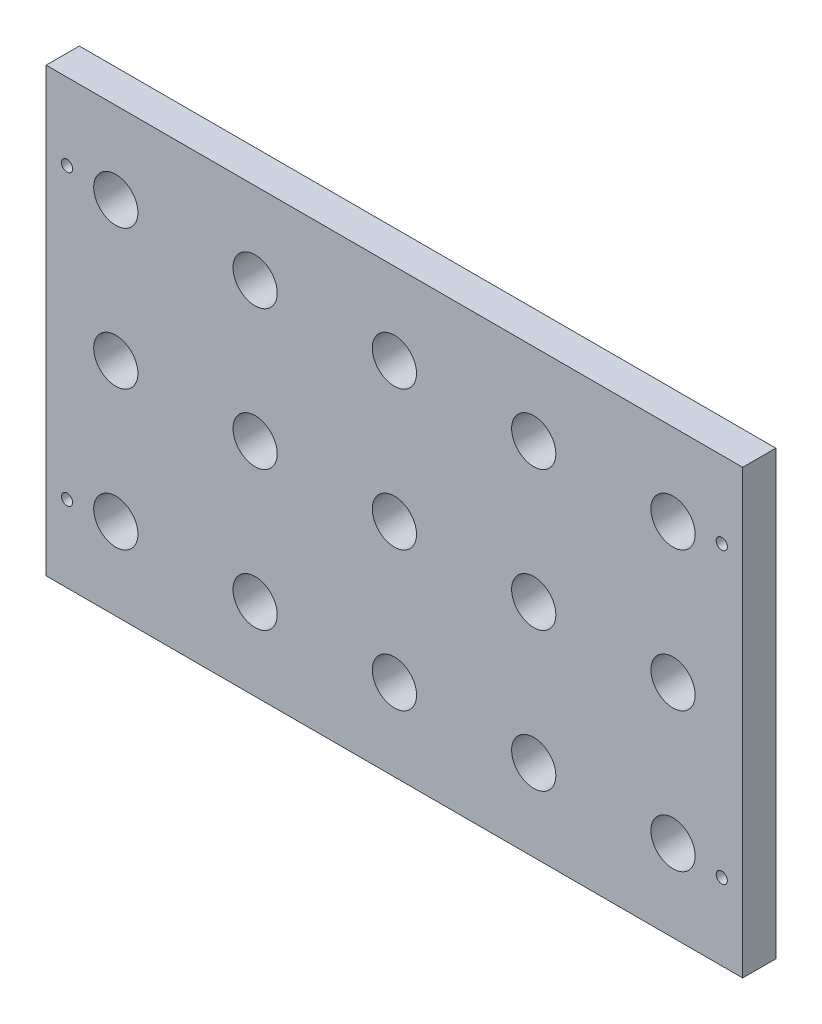
SolidWorks part; units mm, degrees
ref_plane "Front Plane" through (0, 0, 0) normal (0, 0, 1) x (1, 0, 0)
ref_plane "Top Plane" through (0, 0, 0) normal (0, 1, 0) x (1, 0, 0)
ref_plane "Right Plane" through (0, 0, 0) normal (1, 0, 0) x (0, 0, -1)
sketch "Sketch1" plane through (0, 0, 0) normal (0, 0, 1) x (1, 0, 0)
  line L1 (0, 0) -> (200, 0)
  line L2 (0, 0) -> (0, 127)
  line L3 (0, 127) -> (200, 127)
  line L4 (200, 0) -> (200, 127)
  circle A3 centre (6, 105) radius 1.6
  circle A4 centre (6, 22) radius 1.6
  circle A5 centre (194, 22) radius 1.6
  circle A6 centre (194, 105) radius 1.6
  dimension "D11" = 3.2
  dimension "D14" = 3.2
  dimension "D17" = 3.2
  dimension "D22" = 3.2
  dimension "D1" = 127
  dimension "D2" = 200
  dimension "D12" = 6
  dimension "D13" = 22
  dimension "D15" = 6
  dimension "D16" = 22
  dimension "D18" = 6
  dimension "D19" = 22
  dimension "D20" = 6
  dimension "D21" = 22
extrude "Wall" add sketch "Sketch1" along normal blind 9.525
sketch "Sketch2" plane through (0, 0, 9.525) normal (0, 0, 1) x (1, 0, 0)
  line L0 (100, 127) -> (100, 98.425) construction
  line L1 (200, 127) -> (0, 127) construction
  line L2 (100, 98.425) -> (66.6667, 98.425) construction
  line L3 (100, 98.425) -> (133.3333, 98.425) construction
  line L4 (0, 127) -> (0, 0) construction
  circle A0 centre (100, 98.425) radius 3.9687
  circle A1 centre (66.6667, 98.425) radius 3.9688
  circle A2 centre (133.3333, 98.425) radius 3.9687
  dimension "D2" = 7.9375
  dimension "D1" = 28.575
  dimension "D3" = 66.6667
extrude "RodSupportCutouts" [suppressed] cut sketch "Sketch2" against normal up to next
sketch "Sketch3" plane through (0, 0, 9.525) normal (0, 0, 1) x (1, 0, 0)
  line L1 (25.4, 88.9) -> (174.6, 88.9)
  line L2 (25.4, 88.9) -> (25.4, 114.3)
  line L3 (25.4, 114.3) -> (174.6, 114.3)
  line L4 (174.6, 88.9) -> (174.6, 114.3)
  line L5 (25.4, 88.9) -> (174.6, 114.3) construction
  line L6 (25.4, 114.3) -> (174.6, 88.9) construction
  line L7 (200, 127) -> (0, 127) construction
  line L8 (0, 127) -> (0, 0) construction
  point P0 (100, 101.6)
  point P9 (100, 127)
  dimension "D1" = 25.4
  dimension "D2" = 25.4
  dimension "D3" = 25.4
extrude "CannulaLargeCutout" [suppressed] cut sketch "Sketch3" against normal up to next
sketch "Sketch4" plane through (0, 0, 9.525) normal (0, 0, 1) x (1, 0, 0)
  line L0 (6, 103.5) -> (194, 103.5) construction
  line L1 (6, 105) -> (6, 22) construction
  line L2 (194, 105) -> (194, 22) construction
  line L3 (200, 127) -> (0, 127) construction
  line L4 (0, 127) -> (0, 0) construction
  circle A0 centre (60, 103.5) radius 6.35
  circle A1 centre (20, 103.5) radius 6.35
  circle A2 centre (100, 103.5) radius 6.35
  circle A3 centre (140, 103.5) radius 6.35
  circle A4 centre (60, 63.5) radius 6.35
  circle A5 centre (100, 63.5) radius 6.35
  circle A6 centre (140, 63.5) radius 6.35
  circle A7 centre (60, 23.5) radius 6.35
  circle A8 centre (100, 23.5) radius 6.35
  circle A9 centre (140, 23.5) radius 6.35
  circle A10 centre (20, 63.5) radius 6.35
  circle A11 centre (20, 23.5) radius 6.35
  circle A12 centre (180, 103.5) radius 6.35
  circle A13 centre (180, 63.5) radius 6.35
  circle A14 centre (180, 23.5) radius 6.35
  point P42 (100, 127)
  point P45 (0, 63.5)
  dimension "D3" = 12.7
  dimension "D1" = 5
  dimension "D2" = 3
extrude "CannulaHoles" cut sketch "Sketch4" against normal up to next
equation "\"Length\"= 283mm"
equation "\"Width\"= 225mm"
equation "\"WallThickness\"= 12.5mm"
equation "\"UpperWaterJacketThickness\"= 28mm"
equation "\"SpacerHeight\"= 80.2mm"
equation "\"SpacerCornerWidth\"= 10mm"
equation "\"SpacerCornerHeight\"= 60.16mm"
equation "\"SpacerPegDiameter\"= 10mm"
equation "\"SpacerPegHeight\"= 10mm"
equation "\"TubingShort\"= 110mm"
equation "\"TubingLong\"= 175mm"
equation "\"PlateLength\"= 252mm"
equation "\"PlateWidth\"= 190mm"
equation "\"PlateHoleDiameter\"= 5.9mm"
equation "\"PlateHoleBottom\"= 2mm"
equation "\"PlateHoleSide\"= 1.55mm"
equation "\"PlateHoleSpacing\"= 3.1mm"
equation "\"PlateThickness\"= 1.55mm"
equation "\"ReservoirBottom\"= 12.5mm"
equation "\"ReservoirSupportWidth\"= 12mm"
equation "\"ReservoirSupportHeight\"= 15.1mm"
equation "\"ReservoirSupportPlacementHeight\"= 50mm"
equation "\"ReservoirHoleDiameter\"= 12.7mm"
equation "\"ReservoirHoleRight\"= 25mm"
equation "\"ReservoirHoleTop\"= \"ReservoirSupportPlacementHeight\""
equation "\"ReservoirHeight\"= 90mm"
equation "\"ReservoirPortBottom\"= 4mm"
equation "\"ReservoirPortTop\"= 10mm"
equation "\"ReservoirPortWidth\"= 101mm"
equation "\"CustomSpacerWallThickness\"= 0.375in"
equation "\"CustomSpacerHeight\"= 5in"
equation "\"CustomSpacerRodHoleHeight\"= .75in"
equation "\"CustomSpacerRodHoleDiameter\"= .3125in"
equation "\"ScrewBlockSide\"= 12mm"
equation "\"ScrewBlockUpperHeight\"= 16mm"
equation "\"ScrewBlockLowerHeight\"= 16mm"
equation "\"InternalLength\"= \"Length\" - ( 2 * \"WallThickness\" )"
equation "\"InternalWidth\"= \"Width\" - ( 2 * \"WallThickness\" )"
equation "\"CustomSpacerPegHeight\"= 1in"
equation "\"CustomSpacerScrewBore\"=3.2mm"
equation "\"CustomSpacerScrewDepth\"=10mm"
equation "\"D1@Sketch1\"=\"CustomSpacerHeight\""
equation "\"D2@Sketch1\"=\"InternalWidth\""
equation "\"D11@Sketch1\"=\"CustomSpacerScrewBore\""
equation "\"D12@Sketch1\"=\"ScrewBlockSide\"/2"
equation "\"D13@Sketch1\"=\"ScrewBlockUpperHeight\"+\"ScrewBlockSide\"/2"
equation "\"D14@Sketch1\"=\"CustomSpacerScrewBore\""
equation "\"D15@Sketch1\"=\"ScrewBlockSide\"/2"
equation "\"D16@Sketch1\"=\"ScrewBlockLowerHeight\"+\"ScrewBlockSide\"/2"
equation "\"D17@Sketch1\"=\"CustomSpacerScrewBore\""
equation "\"D18@Sketch1\"=\"ScrewBlockSide\"/2"
equation "\"D19@Sketch1\"=\"ScrewBlockUpperHeight\"+\"ScrewBlockSide\"/2"
equation "\"D20@Sketch1\"=\"ScrewBlockSide\"/2"
equation "\"D21@Sketch1\"=\"ScrewBlockLowerHeight\"+\"ScrewBlockSide\"/2"
equation "\"D22@Sketch1\"=\"CustomSpacerScrewBore\""
equation "\"D1@Wall\" = \"CustomSpacerWallThickness\""
equation "\"D1@Sketch2\"=\"CustomSpacerRodHoleHeight\" + \"CustomSpacerRodHoleDiameter\" +0.0625in"
equation "\"D2@Sketch2\"=\"CustomSpacerRodHoleDiameter\""
equation "\"D3@Sketch2\"=\"InternalWidth\" / 3"
equation "\"D1@Sketch3\"=1in"
